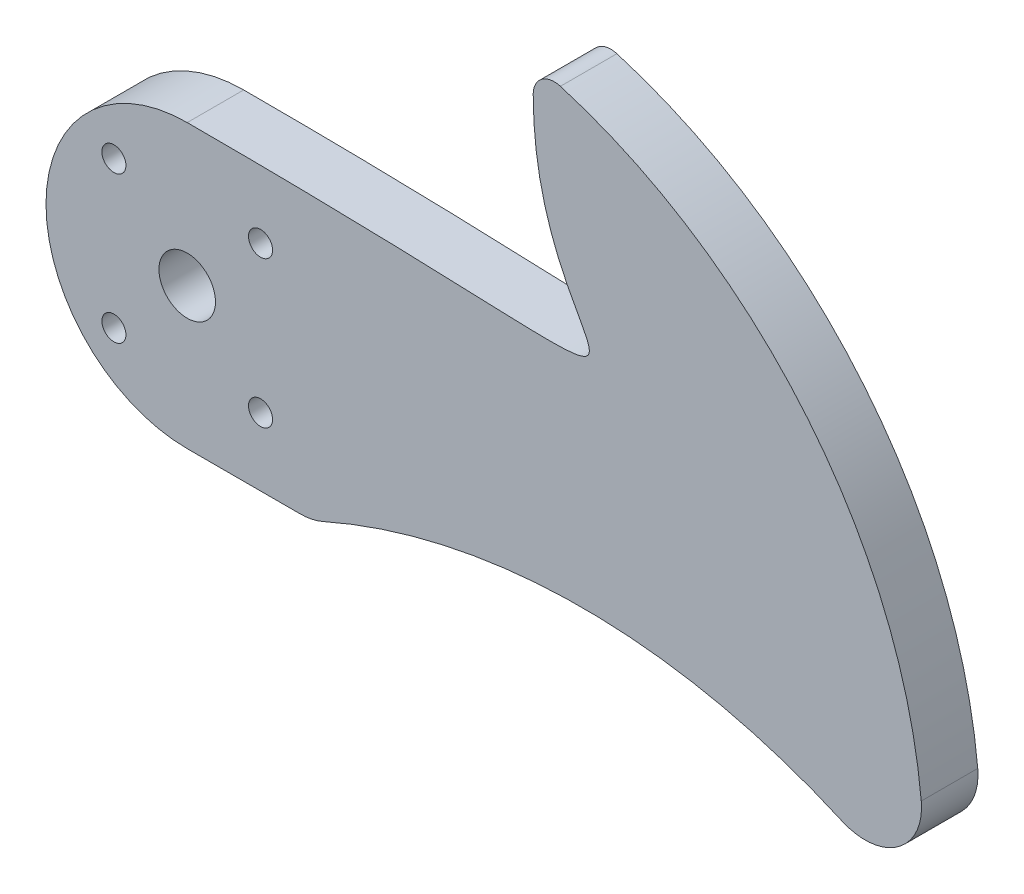
SolidWorks part; units mm, degrees
material "6061 Alloy"
ref_plane "Front" through (0, 0, 0) normal (0, 0, 1) x (1, 0, 0)
ref_plane "Top" through (0, 0, 0) normal (0, 1, 0) x (1, 0, 0)
ref_plane "Right" through (0, 0, 0) normal (1, 0, 0) x (0, 0, -1)
sketch "Sketch1" plane through (0, 0, 0) normal (0, 0, 1) x (1, 0, 0)
  line L0 (0, -15.875) -> (12.7, -15.875)
  line L2 (8.2424, 8.2424) -> (-8.2424, -8.2424) construction
  line L3 (-8.2424, 8.2424) -> (8.2424, -8.2424) construction
  line L4 (0, 0) -> (0, -43.6829) construction
  line L5 (0, -21.8415) -> (119.7815, -21.8415) construction
  line L6 (-8.2424, -51.9253) -> (8.2424, -35.4405) construction
  line L7 (8.2424, -51.9253) -> (-8.2424, -35.4405) construction
  line L8 (3.1238, -59.2475) -> (101.5979, -39.4838) construction
  line L9 (0, -27.8079) -> (101.5979, -27.8079) construction
  line L11 (-22.2168, 15.875) -> (22.2168, 15.875) construction
  line L12 (38.8937, 29.9495) -> (38.8937, 72.4954) construction
  arc A0 (0, 15.875) -> (0, -15.875) centre (0, 0) ccw
  circle A1 centre (0, 0) radius 3.175
  circle A6 centre (0, 0) radius 11.6565 construction
  circle A7 centre (8.2424, 8.2424) radius 1.3525 construction
  circle A8 centre (-8.2424, 8.2424) radius 1.3525 construction
  circle A9 centre (-8.2424, -8.2424) radius 1.3525 construction
  circle A10 centre (8.2424, -8.2424) radius 1.3525 construction
  circle A12 centre (8.2424, -35.4405) radius 1.3525 construction
  circle A13 centre (-8.2424, -35.4405) radius 1.3525 construction
  circle A14 centre (-8.2424, -51.9253) radius 1.3526 construction
  circle A15 centre (8.2424, -51.9253) radius 1.3525 construction
  circle A16 centre (0, -43.6829) radius 11.6565 construction
  arc A17 (101.5979, -27.8079) -> (101.5979, -39.4838) centre (101.5979, -33.6458) cw construction
  circle A18 centre (0, -43.6829) radius 3.175 construction
  arc A19 (3.1238, -59.2475) -> (0, -27.8079) centre (0, -43.6829) cw construction
  circle A20 centre (44.45, -21.8415) radius 25.4 construction
  arc A21 (41.9551, 40.3821) -> (82.5208, -8.9172) centre (25.6333, -14.3876) cw
  arc A25 (41.9551, 40.3821) -> (38.8937, 38.1) centre (41.275, 38.1) ccw
  arc A27 (15.2775, -15.3284) -> (73.6225, -15.3284) centre (44.45, -81.0121) cw
  circle A28 centre (44.45, -21.8415) radius 12.7 construction
  arc A29 (12.7, -15.875) -> (15.2775, -15.3284) centre (12.7, -9.525) ccw
  arc A30 (73.6225, -15.3284) -> (82.5208, -8.9172) centre (76.2, -9.525) ccw
  spline S0 degree 3 poles (38.8937, 38.1) (38.8937, 8.2406) (68.3426, 15.875) (0, 15.875) knots 0 0 0 0 1 1 1 1
  dimension "D1" = 6.35
  dimension "D2" = 31.75
  dimension "D3" = 6.35
  dimension "D4" = 57.15
  dimension "D5" = 43.6829
  dimension "D6" = 50.8
  dimension "D7" = 23.313
  dimension "D8" = 2.7051
  dimension "D10" = 82.55
  dimension "D11" = 63.5
  dimension "D12" = 4.7625
  dimension "D13" = 89.5781
  dimension "D14" = 205.0277
  dimension "D16" = 34.925
  dimension "D17" = 25.4
  dimension "D9" = 38.1
extrude "Boss-Extrude1" add sketch "Sketch1" along normal blind 6.35
hole_wizard "#6-32 Tapped Hole1" positions "Sketch2" profile "Sketch3" tap size "#6-32" standard "ANSI Inch" end condition through all
sketch "Sketch2" plane through (0, 0, 6.35) normal (0, 0, 1) x (1, 0, 0)
  point P0 (8.2424, 8.2424)
  point P3 (-8.2424, 8.2424)
  point P6 (8.2424, -8.2424)
  point P9 (-8.2424, -8.2424)
sketch "Sketch3" plane through (8.2424, 8.2424, 6.35) normal (1, 0, 0) x (0, -1, 0)
  line L0 (0, 0) -> (0, 6.35)
  line L1 (0, 6.35) -> (1.3525, 6.35)
  line L2 (1.3525, 6.35) -> (1.3525, 0)
  line L5 (1.3525, 0) -> (0, 0)
  line L11 (0, -6.35) -> (0, 107.95) construction
  dimension "Thru Tap Drill Dia." = 2.7051
  dimension "Thru Tap Drill Depth" = 6.35
sketch "Sketch4" [suppressed] plane through (0, 0, 6.35) normal (0, 0, 1) x (1, 0, 0)
  circle A0 centre (0, 0) radius 3.175
  circle A1 centre (0, 0) radius 7
  dimension "D1" = 6.35
  dimension "D2" = 14
extrude "Boss-Extrude2" [suppressed] add sketch "Sketch4" along normal blind 1.5875
sketch "Sketch5" plane through (0, 0, 0) normal (0, 0, -1) x (-1, 0, 0)
  circle A0 centre (0, 0) radius 7
  circle A2 centre (0, 0) radius 3.175 construction
  circle A3 centre (0, 0) radius 3.175
  dimension "D2" = 14
extrude "Boss-Extrude3" add sketch "Sketch5" along normal blind 1.5875
sketch "Sketch6" plane through (0, 0, 6.35) normal (0, 0, 1) x (1, 0, 0)
  line L0 (68.326, -15.419) -> (72.3338, -12.2975)
  line L1 (72.3338, -12.2975) -> (73.0332, -17.3291)
  line L2 (68.326, -15.419) -> (73.0332, -17.3291)
  line L3 (72.3338, -12.2975) -> (71.4742, -14.4157) construction
  line L4 (70.2513, -13.9194) -> (72.6972, -14.912) construction
  circle A0 centre (44.45, -81.0121) radius 71.8706 construction
  arc A1 (73.6225, -15.3284) -> (82.5208, -8.9172) centre (76.2, -9.525) ccw construction
  arc A2 (73.6225, -15.3284) -> (15.2775, -15.3284) centre (44.45, -81.0121) ccw construction
  point P10 (71.4742, -14.4157)
  dimension "D1" = 2.286
  dimension "D2" = 2.54
  dimension "D3" = 5.08
extrude "Cut-Extrude1" [suppressed] cut sketch "Sketch6" against normal through all and the other way through all
pattern_curve "CrvPattern1" [suppressed] of bodies 113 parameters "D1"=25, "D3"=50, "D2"=1, "D4"=50
